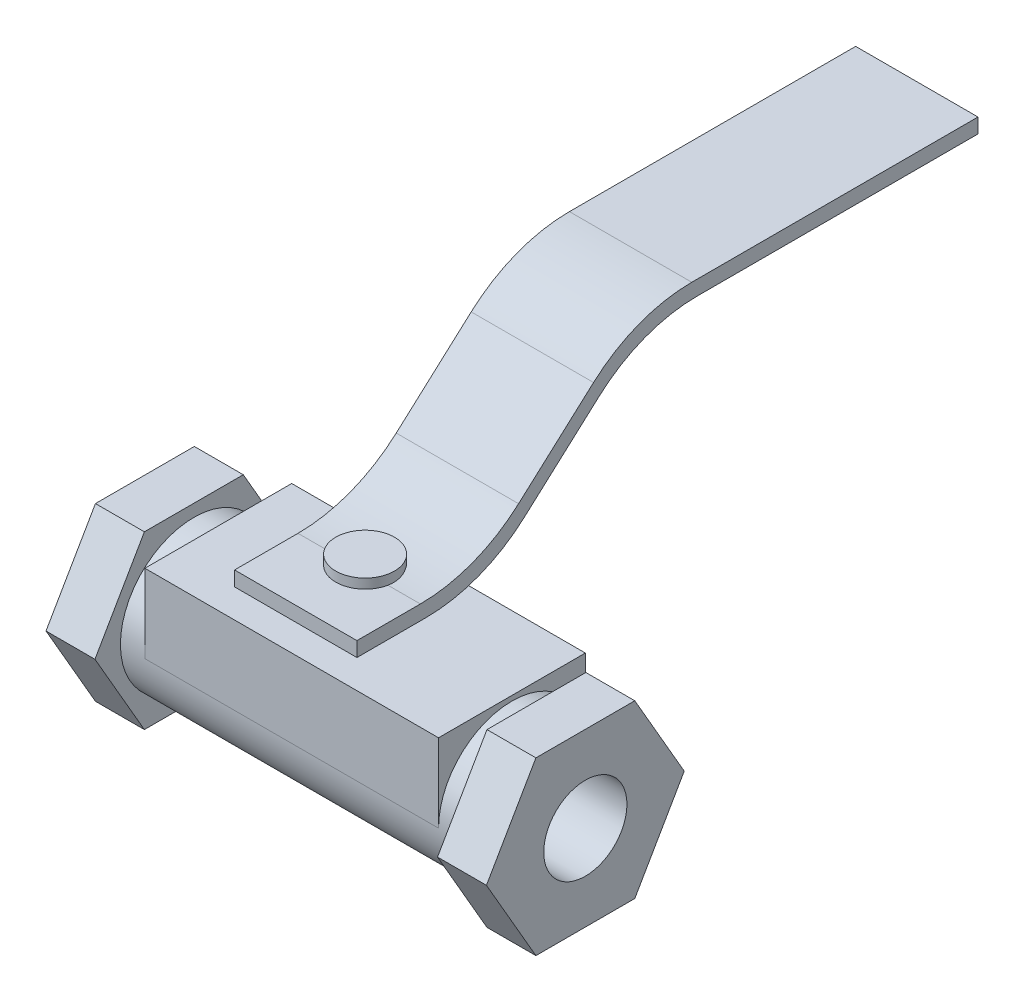
SolidWorks part; units mm, degrees
material "AISI 304"
ref_plane "Front Plane" through (0, 0, 0) normal (0, 0, 1) x (1, 0, 0)
ref_plane "Top Plane" through (0, 0, 0) normal (0, 1, 0) x (1, 0, 0)
ref_plane "Right Plane" through (0, 0, 0) normal (1, 0, 0) x (0, 0, -1)
sketch "Sketch1" plane through (0, 0, 0) normal (1, 0, 0) x (0, 0, -1)
  circle A0 centre (0, 0) radius 15
  dimension "D1" = 30
extrude "Extrude-Thin1" add sketch "Sketch1" along normal mid plane 90 thin thin type one direction reverse wall 10
sketch "Sketch2" plane through (0, 0, 0) normal (0, 1, 0) x (1, 0, 0)
  line L0 (-45, 15) -> (-45, -15) construction
  line L1 (30, -15) -> (-30, -15)
  line L2 (30, -15) -> (30, 15)
  line L3 (30, 15) -> (-30, 15)
  line L4 (-30, -15) -> (-30, 15)
  line L5 (30, -15) -> (-30, 15) construction
  line L6 (30, 15) -> (-30, -15) construction
  point P0 (0, 0)
  dimension "D1" = 15
  dimension "D2" = 30
extrude "Boss-Extrude1" add sketch "Sketch2" along normal blind 16
sketch "Sketch3" plane through (0, 16, 0) normal (0, 1, 0) x (1, 0, 0)
  circle A0 centre (0, 0) radius 6
  dimension "D1" = 12
extrude "Boss-Extrude2" add sketch "Sketch3" along normal blind 10
sketch "Sketch4" plane through (0, 0, 0) normal (1, 0, 0) x (0, 0, -1)
  line L0 (-14.1757, 24.0369) -> (10.3015, 24.0369)
  line L1 (10.3015, 24.0369) -> (42.733, 53.236)
  line L2 (42.733, 53.236) -> (112.733, 53.236)
  dimension "D1" = 70
extrude "Extrude-Thin2" add sketch "Sketch4" along normal mid plane 25 thin thin type one direction wall 3
fillet "Fillet1" radius 30 4 edges at (0, 50.236, -43.8846) (0, 21.0369, -11.453) (0, 24.0369, -10.3015) (0, 53.236, -42.733)
sketch "Sketch5" plane through (45, 0, 0) normal (1, 0, 0) x (0, 0, -1)
  line L1 (-20.2073, 0) -> (-10.1036, -17.5)
  line L2 (-10.1036, -17.5) -> (10.1036, -17.5)
  line L3 (10.1036, -17.5) -> (20.2073, 0)
  line L4 (20.2073, 0) -> (10.1036, 17.5)
  line L5 (10.1036, 17.5) -> (-10.1036, 17.5)
  line L6 (-10.1036, 17.5) -> (-20.2073, 0)
  circle A0 centre (0, 0) radius 17.5 construction
  dimension "D1" = 35
extrude "Boss-Extrude3" add sketch "Sketch5" against normal blind 10
mirror "Mirror1" about plane through (0, 0, 0) normal (1, 0, 0) of "Boss-Extrude3"
sketch "Sketch6" plane through (0, 0, 0) normal (1, 0, 0) x (0, 0, -1)
  circle A0 centre (0, 0) radius 8.5
  dimension "D1" = 17
extrude "Cut-Extrude1" cut sketch "Sketch6" against normal through all both and the other way through all
